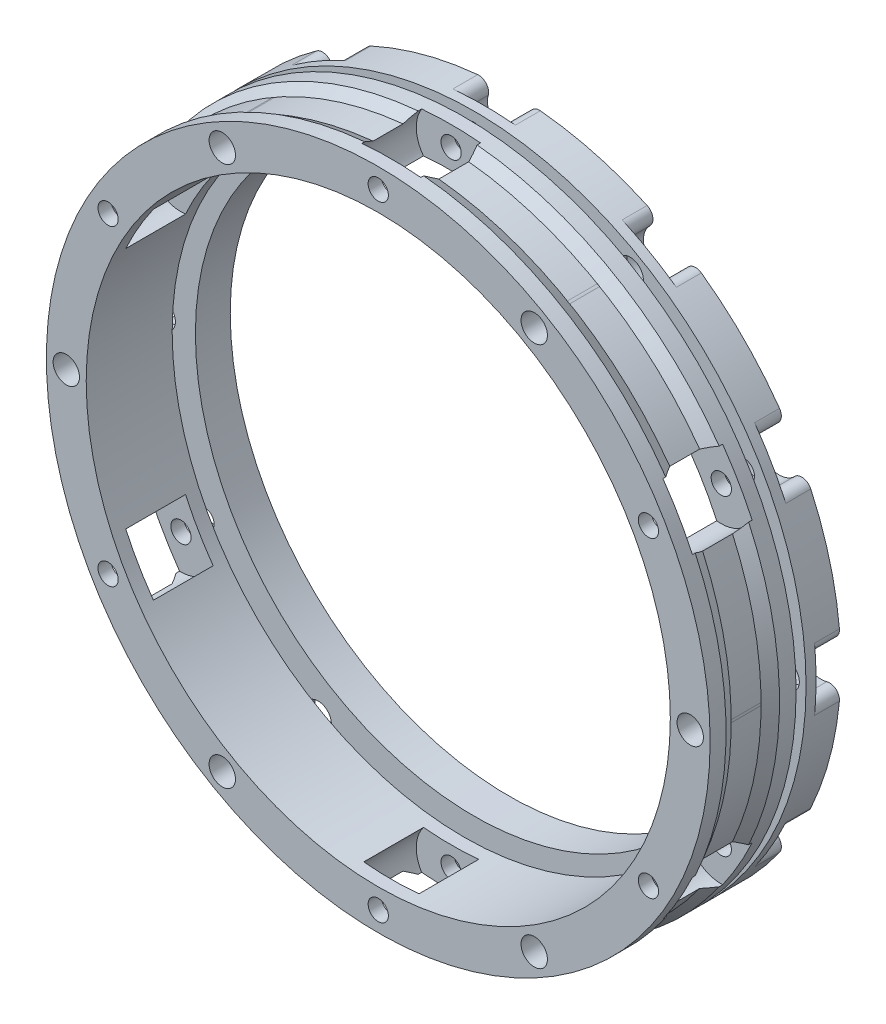
SolidWorks part; units mm, degrees
material "PUR"
ref_plane "Front Plane" through (0, 0, 0) normal (0, 0, 1) x (1, 0, 0)
ref_plane "Top Plane" through (0, 0, 0) normal (0, 1, 0) x (1, 0, 0)
ref_plane "Right Plane" through (0, 0, 0) normal (1, 0, 0) x (0, 0, -1)
sketch "Sketch1" plane through (0, 0, 0) normal (0, 0, 1) x (1, 0, 0)
  circle A0 centre (0, 0) radius 100 construction
  circle A1 centre (0, 0) radius 100
  circle A2 centre (0, 0) radius 88
  dimension "D1" = 12
extrude "Core Structure" add sketch "Sketch1" along normal up to surface (25.9 mm away)
ref_axis "Axis1" through (0, 0, 25.9) along (0, 0, -1)
ref_plane "Midplane" through (0, 0, 12.95) normal (0, 0, 1) x (1, 0, 0)
sketch "Sketch5" plane through (0, 0, -3) normal (0, 0, 1) x (1, 0, 0)
  circle A0 centre (0, 0) radius 100 construction
  circle A1 centre (0, 0) radius 88 construction
  circle A2 centre (0, 0) radius 100
  circle A3 centre (0, 0) radius 88 construction
  circle A4 centre (0, 0) radius 84
  dimension "D1" = 4
extrude "Hover Brim" add sketch "Sketch5" against normal blind 10.5 separate body
sketch "Sketch3" plane through (0, 0, 12.95) normal (0, 0, 1) x (1, 0, 0)
  circle A0 centre (0, 94) radius 3 construction
  circle A1 centre (0, 94) radius 3 construction
  circle A2 centre (0, 94) radius 10.5
  dimension "D1" = 21
extrude "Bearing Hole" cut sketch "Sketch3" against normal mid plane 18
sketch "Sketch6" plane through (0, 0, 21.95) normal (0, 0, -1) x (-1, 0, 0)
  circle A0 centre (0, 94) radius 3.05
  arc A4 (-8.8788, 99.6051) -> (-8.3279, 87.6051) centre (0, 94) ccw
  arc A5 (8.3279, 87.6051) -> (-8.3279, 87.6051) centre (0, 0) ccw
  arc A6 (8.3279, 87.6051) -> (8.8788, 99.6051) centre (0, 94) ccw
  arc A7 (8.8788, 99.6051) -> (-8.8788, 99.6051) centre (0, 0) ccw
  arc A8 (-8.8788, 99.6051) -> (-8.3279, 87.6051) centre (0, 94) ccw construction
  arc A9 (8.3279, 87.6051) -> (-8.3279, 87.6051) centre (0, 0) ccw construction
  arc A10 (8.3279, 87.6051) -> (8.8788, 99.6051) centre (0, 94) ccw construction
  arc A11 (8.8788, 99.6051) -> (-8.8788, 99.6051) centre (0, 0) ccw construction
  dimension "D2" = 6.1
  dimension "D1" = 0
extrude "Bearing Mounting Hole" cut sketch "Sketch6" against normal through all both and the other way through all
sketch "Sketch2" plane through (0, 0, 25.9) normal (0, 0, 1) x (1, 0, 0)
  circle A0 centre (47, 81.4064) radius 3.9751 construction
  circle A1 centre (47, 81.4064) radius 3.9751
extrude "Structural Hole" cut sketch "Sketch2" against normal through all both and the other way through all
pattern_circular "CirPattern1" count 6 over 360 about axis through (0, 0, 25.9) along (0, 0, -1) of "Bearing Hole", "Structural Hole", "Bearing Mounting Hole" reverse direction yes
sketch "Sketch7" plane through (0, 0, -13.5) normal (0, 0, -1) x (-1, 0, 0)
  circle A0 centre (-47, 81.4064) radius 6.5
  circle A1 centre (0, 94) radius 6.5
  dimension "D1" = 13
  dimension "D2" = 13
extrude "Cut-Extrude5" cut sketch "Sketch7" against normal blind 7.5
fillet "Fillet2" radius 3 4 edges at (2.5783, 99.9668, -9.75) (-2.5783, 99.9668, -9.75) (52.2163, 85.2846, -9.75) (47.7505, 87.8629, -9.75)
sketch "Sketch4" plane through (0, 0, 0) normal (0, 1, 0) x (1, 0, 0)
  line L0 (99, -8.55) -> (-99, -8.55) construction
  line L1 (99, -8.55) -> (-99, -8.55) construction
  line L2 (-99, -17.55) -> (99, -17.55) construction
  line L3 (-99, -17.55) -> (99, -17.55) construction
  line L4 (-100, 0) -> (-100, -25.9) construction
  line L5 (-100, 0) -> (-100, -25.9) construction
  line L7 (-98, -17.55) -> (-98, -8.55)
  line L9 (-98, -17.55) -> (-100, -21.1)
  line L10 (-100, -21.1) -> (-100, -5)
  line L11 (-100, -5) -> (-98, -8.55)
  line L12 (-98, -13.05) -> (-100, -13.05) construction
  line L13 (0, 0) -> (0, -45.0086) construction
  dimension "D1" = 5
  dimension "D2" = 1
revolve "Cut-Revolve1" cut sketch "Sketch4" angle 360 about L13
pattern_circular "CirPattern13" count 6 over 360 about axis through (0, 0, 25.9) along (0, 0, -1) of "Cut-Extrude5", "Fillet2"
